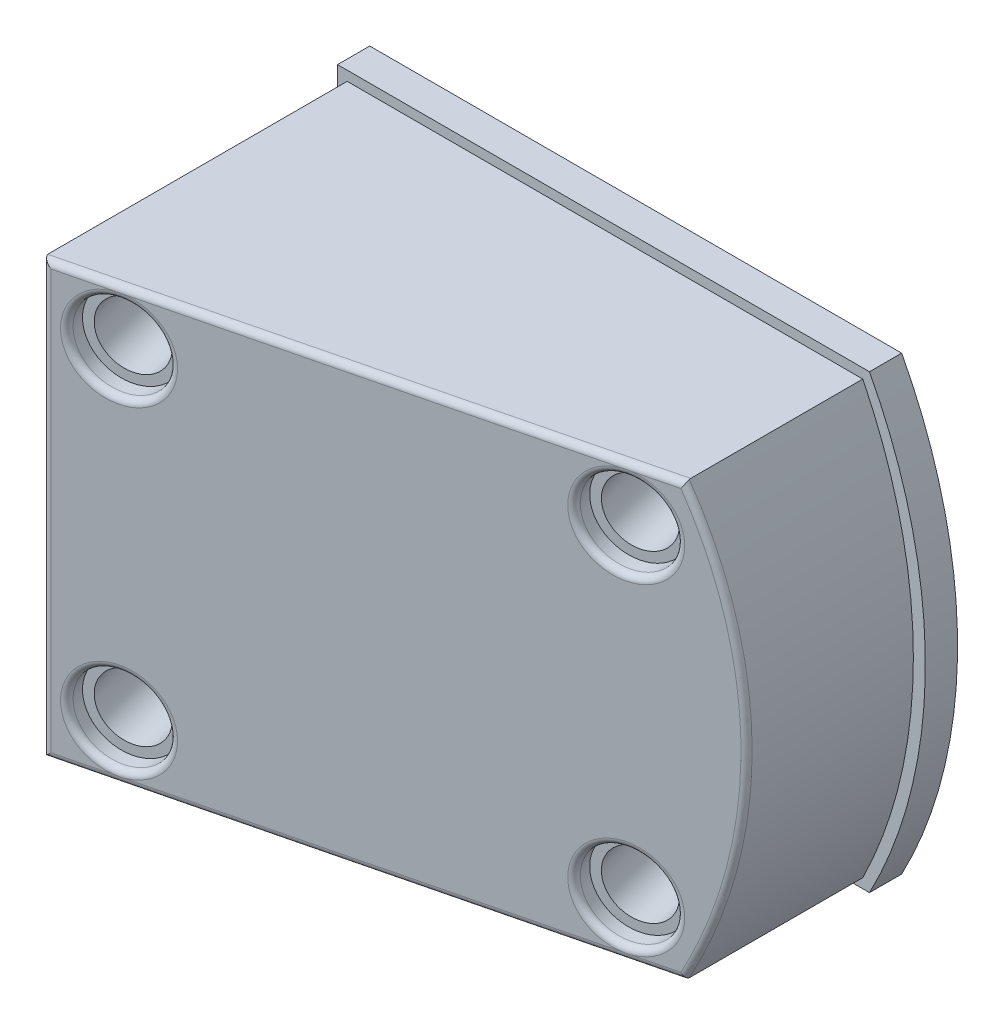
SolidWorks part; units mm, degrees
ref_plane "Front Plane" through (0, 0, 0) normal (0, 0, 1) x (1, 0, 0)
ref_plane "Top Plane" through (0, 0, 0) normal (0, 1, 0) x (1, 0, 0)
ref_plane "Right Plane" through (0, 0, 0) normal (1, 0, 0) x (0, 0, -1)
sketch "Sketch1" plane through (0, 0, 0) normal (0, 0, 1) x (1, 0, 0)
  line L6 (-16.2049, 35) -> (-16.2049, -35)
  line L7 (-16.2049, -35) -> (66.3325, -35)
  line L8 (66.3325, 35) -> (-16.2049, 35)
  arc A2 (66.3325, -35) -> (66.3325, 35) centre (0, 0) ccw
extrude "Boss-Extrude1" add sketch "Sketch1" along normal blind 5
sketch "Sketch2" plane through (0, 0, 5) normal (0, 0, 1) x (1, 0, 0)
  line L0 (65.2951, 33.5) -> (-14.7049, 33.5)
  line L1 (-14.7049, 33.5) -> (-14.7049, -33.5)
  line L2 (-14.7049, -33.5) -> (65.2951, -33.5)
  line L5 (66.3325, 35) -> (-16.2049, 35) construction
  arc A0 (65.2951, -33.5) -> (65.2951, 33.5) centre (-2.2981, 0) ccw
  dimension "D3" = 1.5
  dimension "D5" = 12.4068
  dimension "D6" = 80
extrude "Boss-Extrude2" add sketch "Sketch2" along normal up to surface (47.5024 mm away)
sketch "Sketch3" plane through (11.3798, 0, 46.0575) normal (0.2399, 0, 0.9708) x (0.9708, 0, -0.2399)
  line L1 (-26.869, -33.5) -> (-26.869, 33.5) construction
  circle A0 centre (-16.869, 25) radius 5
  circle A1 centre (-16.869, -25) radius 5
  circle A2 centre (48.131, -25) radius 5
  circle A3 centre (48.131, 25) radius 5
  dimension "D1" = 10
  dimension "D2" = 10
  dimension "D3" = 10
  dimension "D4" = 10
  dimension "D6" = 65
  dimension "D9" = 10
  dimension "D12" = 65
  dimension "D10" = 10
extrude "Cut-Extrude1" cut sketch "Sketch3" against normal blind 25
sketch "Sketch4" plane through (11.3798, 0, 46.0575) normal (0.2399, 0, 0.9708) x (0.9708, 0, -0.2399)
  line L0 (48.131, 30) -> (48.131, -30) construction
  line L1 (53.131, 25) -> (43.131, 25) construction
  line L2 (43.131, -25) -> (53.131, -25) construction
  circle A1 centre (48.131, 25) radius 5 construction
  circle A2 centre (48.131, 25) radius 5 construction
  circle A3 centre (48.131, -25) radius 5 construction
  circle A4 centre (48.131, -25) radius 5 construction
  circle A8 centre (-16.869, 25) radius 6.5
  circle A9 centre (-16.869, -25) radius 6.5
  circle A10 centre (48.131, -25) radius 6.5
  circle A11 centre (48.131, 25) radius 6.5
  dimension "D1" = 13
  dimension "D2" = 13
  dimension "D3" = 13
  dimension "D4" = 13
extrude "Cut-Extrude2" cut sketch "Sketch4" against normal blind 3
fillet "Fillet1" radius 1 8 edges at (73.1412, 0, 30.7977) (25.2951, -33.5, 42.6194) (-14.7049, 0, 52.5024) (25.2951, 33.5, 42.6194) (64.4158, -25, 32.9535) (64.4158, 25, 32.9535) (1.3134, 25, 48.5447) (1.3134, -25, 48.5447)
sketch3d "URDF Reference"
  point P0 (0, 0, 0)
